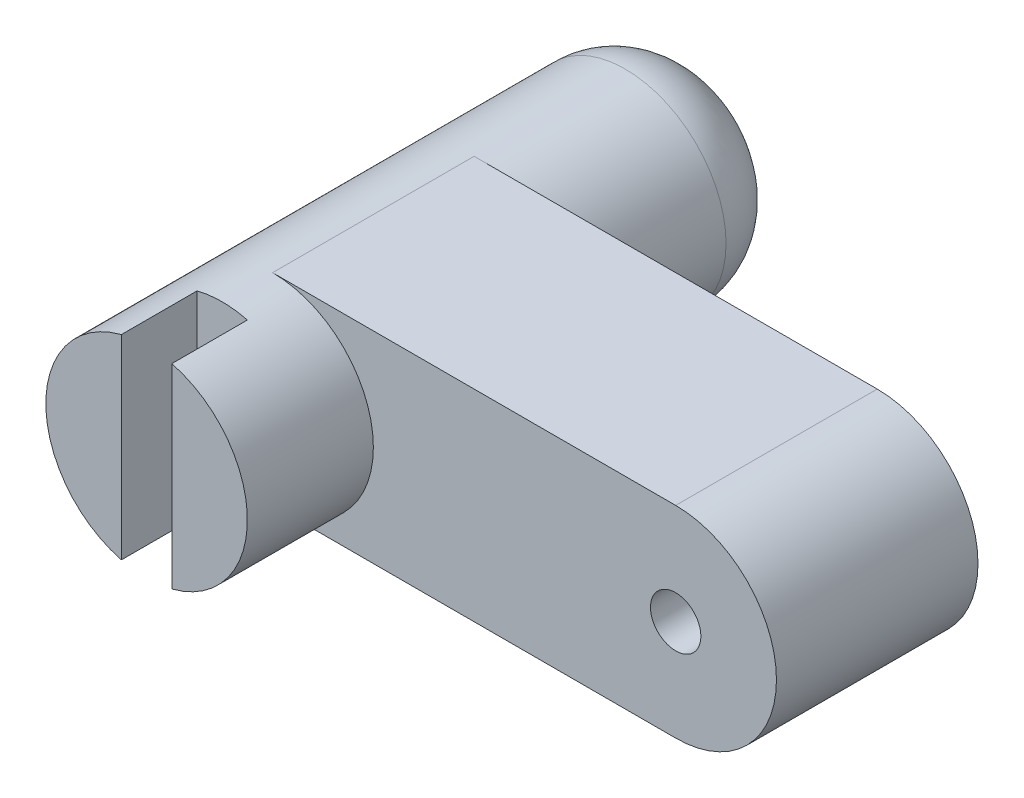
SolidWorks part; units mm, degrees
ref_plane "前视基准面" through (0, 0, 0) normal (0, 0, 1) x (1, 0, 0)
ref_plane "上视基准面" through (0, 0, 0) normal (0, 1, 0) x (1, 0, 0)
ref_plane "右视基准面" through (0, 0, 0) normal (1, 0, 0) x (0, 0, -1)
other "Configuration Table"
sketch "草图1" plane through (0, 0, 0) normal (0, 0, 1) x (1, 0, 0)
  circle A0 centre (0, 0) radius 2
  circle A1 centre (0, 0) radius 0.5
  dimension "D1" = 4
  dimension "D2" = 1
extrude "凸台-拉伸1" add sketch "草图1" along normal blind 11
sketch "草图2" plane through (0, 0, 11) normal (0, 0, 1) x (1, 0, 0)
  line L1 (-0.5, -2.0824) -> (0.5, -2.0824)
  line L2 (-0.5, -2.0824) -> (-0.5, 2.0824)
  line L3 (-0.5, 2.0824) -> (0.5, 2.0824)
  line L4 (0.5, -2.0824) -> (0.5, 2.0824)
  line L5 (-0.5, -2.0824) -> (0.5, 2.0824) construction
  line L6 (-0.5, 2.0824) -> (0.5, -2.0824) construction
  point P0 (0, 0)
  dimension "D1" = 1
extrude "切除-拉伸1" cut sketch "草图2" against normal blind 1.5
fillet "圆角2" radius 1.5 1 edges at (2, 0, 0)
sketch "草图3" plane through (0, 0, 0) normal (0, 1, 0) x (1, 0, 0)
  line L0 (0, 0) -> (0, -4.5) construction
  line L1 (0, -4.5) -> (0, -8.5)
  line L2 (0, -4.5) -> (8, -4.5)
  line L3 (8, -4.5) -> (8, -8.5)
  line L4 (0, -8.5) -> (8, -8.5)
  dimension "D1" = 4.5
  dimension "D2" = 4
  dimension "D3" = 8
  dimension "D4" = 4
extrude "凸台-拉伸2" add sketch "草图3" along normal mid plane 4
sketch "草图4" plane through (0, 0, 4.5) normal (0, 0, -1) x (-1, 0, 0)
  line L0 (-8, 2) -> (-8, -2) construction
  circle A0 centre (-8, 0) radius 2
  circle A1 centre (-8, 0) radius 0.5
  dimension "D1" = 1
extrude "凸台-拉伸3" add sketch "草图4" against normal blind 4
sketch "草图5" plane through (0, 0, 4.5) normal (0, 0, -1) x (-1, 0, 0)
  line L0 (-8, 0.5) -> (-8, -0.5) construction
  circle A0 centre (-8, 0) radius 0.5
  dimension "D1" = 1
extrude "切除-拉伸2" cut sketch "草图5" against normal blind 4
sketch "草图6" plane through (0, 0, 11) normal (0, 0, 1) x (1, 0, 0)
  circle A0 centre (0, 0) radius 0.5
  dimension "D1" = 1
extrude "切除-拉伸3" cut sketch "草图6" against normal through all
